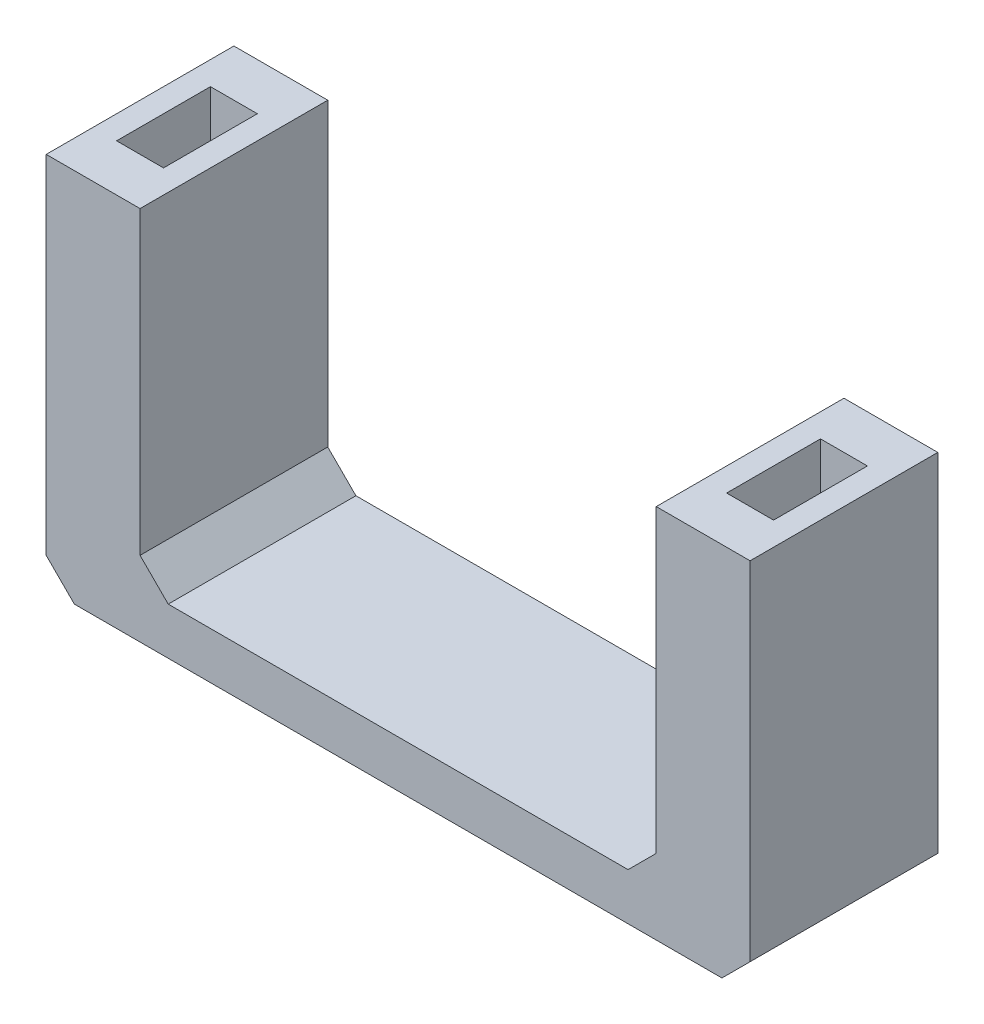
SolidWorks part; units mm, degrees
ref_plane "Front" through (0, 0, 0) normal (0, 0, 1) x (1, 0, 0)
ref_plane "Top" through (0, 0, 0) normal (0, 1, 0) x (1, 0, 0)
ref_plane "Right" through (0, 0, 0) normal (1, 0, 0) x (0, 0, -1)
sketch "Sketch1" plane through (0, 0, 0) normal (0, 1, 0) x (1, 0, 0)
  circle A0 centre (0, 0) radius 250
  dimension "D1" = 500
extrude "Boss-Extrude1" add sketch "Sketch1" along normal blind 250
sketch "Sketch3" plane through (0, 250, 0) normal (0, 1, 0) x (1, 0, 0)
  line L1 (-1375, -500) -> (1375, -500)
  line L2 (-1375, -500) -> (-1375, 500)
  line L3 (-1375, 500) -> (1375, 500)
  line L4 (1375, -500) -> (1375, 500)
  line L5 (-1375, -500) -> (1375, 500) construction
  line L6 (-1375, 500) -> (1375, -500) construction
  point P0 (0, 0)
  dimension "D1" = 2750
  dimension "D2" = 1000
extrude "Boss-Extrude3" add sketch "Sketch3" along normal mid plane 250
sketch "Sketch4" plane through (1375, 0, 0) normal (1, 0, 0) x (0, 0, -1)
  line L0 (500, 375) -> (500, 125) construction
  line L1 (-500, 125) -> (500, 125)
  line L2 (-500, 125) -> (-500, 2125)
  line L3 (-500, 2125) -> (500, 2125)
  line L4 (500, 125) -> (500, 2125)
  dimension "D1" = 2000
extrude "Boss-Extrude4" add sketch "Sketch4" along normal blind 500
sketch "Sketch6" plane through (0, 125, 0) normal (0, -1, 0) x (1, 0, 0)
  line L0 (1375, 0) -> (1875, 0) construction
  line L1 (1500, -250) -> (1750, -250)
  line L2 (1500, -250) -> (1500, 250)
  line L3 (1500, 250) -> (1750, 250)
  line L4 (1375, 500) -> (1375, -500)
  line L5 (1875, 500) -> (1375, 500)
  line L6 (1875, -500) -> (1875, 500)
  line L7 (1375, -500) -> (1875, -500)
  line L8 (1375, 500) -> (1375, -500) construction
  line L9 (1875, 500) -> (1375, 500) construction
  line L10 (1875, -500) -> (1875, 500) construction
  line L11 (1375, -500) -> (1875, -500) construction
  line L12 (1750, -250) -> (1750, 250)
  line L13 (1500, -250) -> (1750, 250) construction
  line L14 (1500, 250) -> (1750, -250) construction
  line L15 (1625, 500) -> (1625, -500) construction
  point P2 (1625, 0)
  point P13 (0, 0)
  point P14 (0, 0)
  dimension "D2" = 500
  dimension "D3" = 250
  dimension "D1" = 0
extrude "Cut-Extrude1" cut sketch "Sketch6" against normal blind 2597
sketch "Sketch7" plane through (0, 125, 0) normal (0, -1, 0) x (1, 0, 0)
  line L1 (1500, -250) -> (1750, -250) construction
  line L3 (1750, 250) -> (1500, 250) construction
  line L4 (1625, 250) -> (1625, -250) construction
  line L5 (1750, 0) -> (1500, 0) construction
  line L6 (1750, -250) -> (1750, 250) construction
  line L7 (1500, 250) -> (1500, -250) construction
  line L9 (1500, -400) -> (1750, -400)
  line L10 (1500, -400) -> (1500, 400)
  line L11 (1500, 400) -> (1750, 400)
  line L12 (1750, -400) -> (1750, 400)
  line L13 (1500, -400) -> (1750, 400) construction
  line L14 (1500, 400) -> (1750, -400) construction
  point P12 (1625, 0)
  dimension "D1" = 250
  dimension "D2" = 800
extrude "Cut-Extrude2" cut sketch "Sketch7" against normal blind 1750
chamfer "Chamfer1" distance 150 angle 45 2 edges at (1875, 125, 0) (1375, 375, 0)
mirror "Mirror1" about plane through (0, 0, 0) normal (1, 0, 0) of "Cut-Extrude2", "Cut-Extrude1", "Boss-Extrude4", "Chamfer1"
equation "\"BaseDiameter\"= .5"
equation "\"D1@Sketch1\"=\"BaseDiameter\""
equation "\"BaseHeight\"=0.25"
equation "\"D1@Boss-Extrude1\"=\"BaseHeight\""
equation "\"topdiameter\"=1"
equation "\"topheight\"=0.25"
